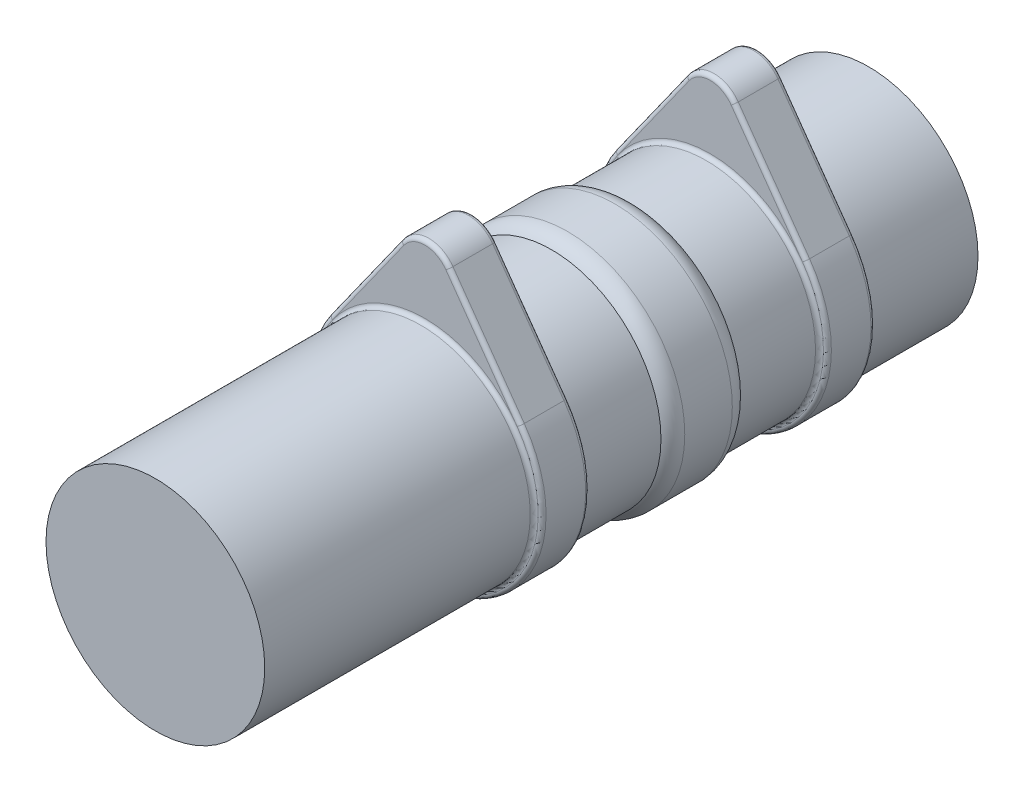
SolidWorks part; units mm, degrees
ref_plane "Front Plane" through (0, 0, 0) normal (0, 0, 1) x (1, 0, 0)
ref_plane "Top Plane" through (0, 0, 0) normal (0, 1, 0) x (1, 0, 0)
ref_plane "Right Plane" through (0, 0, 0) normal (1, 0, 0) x (0, 0, -1)
sketch "Sketch1" plane through (0, 0, 0) normal (0, 0, 1) x (1, 0, 0)
  line L0 (0, 0) -> (0, 13.8) construction
  circle A0 centre (0, 0) radius 13.8
  dimension "D1" = 27.6
extrude "Boss-Extrude1" add sketch "Sketch1" against normal blind 34
sketch "Sketch3" plane through (0, 0, -34) normal (0, 0, -1) x (-1, 0, 0)
  line L0 (0, 0) -> (0, 22.8) construction
  line L1 (-3.0547, 21.2252) -> (-12.0558, 8.5848)
  line L2 (3.0547, 21.2252) -> (12.0558, 8.5848)
  arc A0 (-12.0558, 8.5848) -> (12.0558, 8.5848) centre (0, 0) ccw
  arc A1 (3.0547, 21.2252) -> (-3.0547, 21.2252) centre (0, 19.05) ccw
  dimension "D1" = 29.6
  dimension "D3" = 7.5
  dimension "D2" = 22.8
extrude "Boss-Extrude2" add sketch "Sketch3" along normal blind 6
sketch "Sketch4" plane through (0, 0, -40) normal (0, 0, -1) x (-1, 0, 0)
  circle A0 centre (0, 0) radius 13.8
  dimension "D1" = 27.6
extrude "Boss-Extrude3" add sketch "Sketch4" along normal blind 10
sketch "Sketch5" plane through (0, 0, -50) normal (0, 0, -1) x (-1, 0, 0)
  circle A0 centre (0, 0) radius 14.8
  dimension "D1" = 29.6
extrude "Boss-Extrude4" add sketch "Sketch5" along normal blind 10
sketch "Sketch6" plane through (0, 0, -60) normal (0, 0, -1) x (-1, 0, 0)
  circle A0 centre (0, 0) radius 13.8
  dimension "D1" = 27.6
extrude "Boss-Extrude5" add sketch "Sketch6" along normal blind 10
fillet "Fillet1" radius 2.5 2 edges at (-14.8, 0, -50) (-14.8, 0, -60)
sketch "Sketch7" plane through (0, 0, -70) normal (0, 0, -1) x (-1, 0, 0)
  line L0 (-3.0547, 21.2252) -> (-12.0558, 8.5848)
  line L1 (3.0547, 21.2252) -> (12.0558, 8.5848)
  line L2 (12.0558, 8.5848) -> (3.0547, 21.2252) construction
  arc A0 (-12.0558, 8.5848) -> (12.0558, 8.5848) centre (0, 0) ccw
  arc A1 (3.0547, 21.2252) -> (-3.0547, 21.2252) centre (0, 19.05) ccw
  dimension "D1" = 29.6
extrude "Boss-Extrude6" add sketch "Sketch7" along normal blind 6
fillet "Fillet2" radius 0.5 19 edges at (-7.5552, 14.905, -40) (0, -14.8, -40) (7.5552, 14.905, -40) (0, 22.8, -40) (-13.8, 0, -40) (7.5552, 14.905, -34) (0, -14.8, -34) (-7.5552, 14.905, -34) (0, 22.8, -34) (13.8, 0, -34) (7.5552, 14.905, -70) (0, -14.8, -70) (-7.5552, 14.905, -70) (0, 22.8, -70) (-13.8, 0, -70) (-7.5552, 14.905, -76) (0, -14.8, -76) (7.5552, 14.905, -76) (0, 22.8, -76)
sketch "Sketch8" plane through (0, 0, -76) normal (0, 0, -1) x (-1, 0, 0)
  circle A0 centre (0, 0) radius 13.8
  dimension "D1" = 27.6
extrude "Boss-Extrude8" add sketch "Sketch8" along normal blind 14
